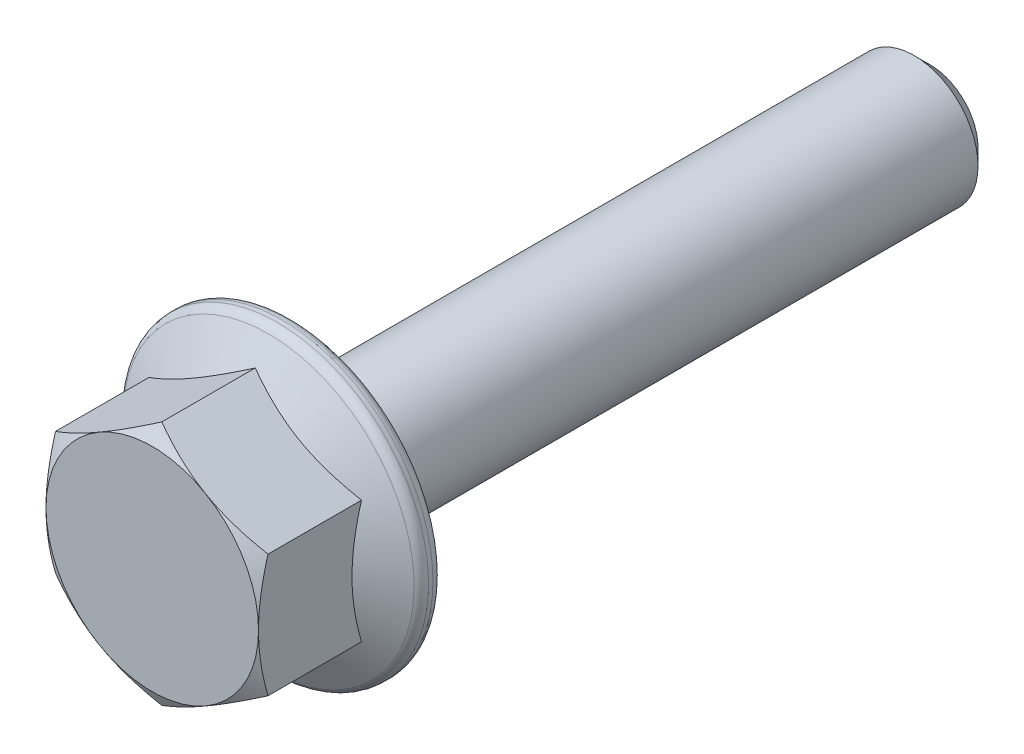
SolidWorks part; units mm, degrees
ref_plane "Front" through (0, 0, 0) normal (0, 0, 1) x (1, 0, 0)
ref_plane "Top" through (0, 0, 0) normal (0, 1, 0) x (1, 0, 0)
ref_plane "Right" through (0, 0, 0) normal (1, 0, 0) x (0, 0, -1)
sketch "Sketch1" plane through (0, 0, 0) normal (0, 0, 1) x (1, 0, 0)
  line L1 (5, -2.8868) -> (5, 2.8868)
  line L2 (5, 2.8868) -> (0, 5.7735)
  line L3 (0, 5.7735) -> (-5, 2.8868)
  line L4 (-5, 2.8868) -> (-5, -2.8868)
  line L5 (-5, -2.8868) -> (0, -5.7735)
  line L6 (0, -5.7735) -> (5, -2.8868)
  circle A0 centre (0, 0) radius 5 construction
extrude "Extrude1" add sketch "Sketch1" along normal blind 6.6
sketch "Sketch2" plane through (0, 0, 0) normal (0, 0, -1) x (-1, 0, 0)
  circle A0 centre (0, 0) radius 7.1
  dimension "Washer OD" = 14.2
extrude "Extrude2" add sketch "Sketch2" against normal blind 0.99
sketch "Sketch5" plane through (0, 0, 0) normal (1, 0, 0) x (0, 0, -1)
  line L0 (0, 0) -> (30, 0)
  line L3 (30, 0) -> (30, 3)
  line L4 (30, 3) -> (0, 3)
  line L5 (0, -7.1) -> (0, 7.1) construction
  line L6 (0, 3) -> (0, 0)
  line L7 (30, 0) -> (33.175, 0) construction
  line L8 (30, -3) -> (0, -3) construction
  line L9 (0, 3) -> (0, 7.1) construction
  line L10 (0, -7.1) -> (0, 7.1) construction
  dimension "Screw Dia" = 6
  dimension "Drill Length" = 3.175
  dimension "Body Length" = 30
  dimension "Screw Length" = 30
sketch "Sketch4" plane through (0, 0, 6.6) normal (0, 0, 1) x (1, 0, 0)
  circle A0 centre (0, 0) radius 4.5
  dimension "D1" = 9
extrude "Cut-Extrude1" [suppressed] cut sketch "Sketch4" against normal blind 0.25 draft 45
sketch "Sketch15" plane through (0, 0, 6.6) normal (0, 0, 1) x (1, 0, 0)
  line L0 (5, 2.8868) -> (0, 5.7735) construction
  circle A0 centre (0, 0) radius 5
extrude "Cut-Extrude5" cut sketch "Sketch15" against normal blind 6.6 draft 60 flip side to cut
revolve "Revolve1" add sketch "Sketch5" angle 360 about L7
sketch "Sketch6" plane through (0, 0, 0) normal (0, 0, 1) x (1, 0, 0)
  circle A0 centre (0, 0) radius 3 construction
  circle A1 centre (0, 0) radius 3
curve "Helix/Spiral1" [suppressed] pitch 1 height 31 turns 31 parameters "Pitch"=1
sketch "Sketch7" plane through (0, 0, 0) normal (1, 0, 0) x (0, 0, -1)
  line L0 (-0.1875, 2.6752) -> (-0.6875, 2.6752) construction
  line L1 (0, 3) -> (0, 0) construction
  line L2 (-0.875, 3) -> (-0.5, 2.3505)
  line L3 (-0.5, 2.3505) -> (-0.375, 2.3505)
  line L4 (-0.375, 2.3505) -> (0, 3)
  line L5 (0, 3) -> (-0.875, 3)
  line L6 (-0.4375, 2.3505) -> (-0.4375, 3) construction
  line L7 (0, 3) -> (0, -8) construction
  line L8 (0, 3) -> (0, -3) construction
  dimension "D3" = 0.125
  dimension "D4" = 60
  dimension "D1" = 0.5
chamfer "Chamfer1" distance 0.75 angle 45 1 edges at (3, 0, -30)
sweep "Cut-Sweep1" [suppressed] cut profiles "Sketch7" path "Helix/Spiral1"
combine bodies "Combine1" operation type add bodies to combine 137 112
sketch "Sketch10" plane through (0, 0, 0) normal (1, 0, 0) x (0, 0, -1)
  line L0 (12, 2.3505) -> (11.6971, 3)
  line L1 (-0.875, 3) -> (11.6971, 3)
  line L2 (-0.875, 3) -> (-0.875, 0)
  line L3 (-0.875, 0) -> (12, 0)
  line L4 (12, 2.3505) -> (12, 0)
  line L6 (30, -2.25) -> (30, 2.25) construction
  dimension "D1" = 25
  dimension "Min Thread" = 18
revolve "Revolve2" add sketch "Sketch10" angle 360 about L3
sketch "Sketch11" plane through (0, 0, 0.99) normal (0, 0, 1) x (1, 0, 0)
  circle A0 centre (0, 0) radius 7.1 construction
  circle A1 centre (0, 0) radius 7.1
extrude "Extrude3" add sketch "Sketch11" along normal blind 3.3 draft 60
sketch "Sketch12" plane through (0, 0, 0) normal (1, 0, 0) x (0, 0, -1)
  line L0 (30, 3) -> (30, -3) construction
  line L1 (0, 0) -> (30, 0) construction
  line L3 (28.5, 3) -> (28.5, -3) construction
  line L4 (30, -2.25) -> (30, 2.25) construction
  dimension "D1" = 1.5
sketch "Sketch13" [suppressed] plane through (0, 0, 6.35) normal (0, 0, 1) x (1, 0, 0)
  line L0 (-5, 2.8868) -> (-5, -2.8868) construction
  line L1 (5, -1.2) -> (-5, -1.2) construction
  line L2 (5, -2.8868) -> (5, 2.8868) construction
  text T0 "10.9" font "Arial" height in points 11
  point P8 (0, -1.2)
  dimension "D1" = 1.2
extrude "Cut-Extrude2" [suppressed] cut sketch "Sketch13" against normal blind 0.25
fillet "Fillet1" radius 0.495 2 edges at (-7.1, 0, 0) (7.1, 0, 0.99)
equation "\"D1@Cut-Extrude1\"=\"Hex@Sketch1\"  * 1 / 40"
equation "\"D3@Helix/Spiral1\" = \"Screw Length@Sketch5\" + \"Pitch@Helix/Spiral1\""
equation "\"D3@Sketch7\" = \"Pitch@Helix/Spiral1\" * 1 / 8"
equation "\"D1@Sketch7\" = \"Pitch@Helix/Spiral1\" * 1 / 2"
equation "\"D1@Sketch12\" = \"Pitch@Helix/Spiral1\" * 1.5"
equation "\"D1@Extrude3\" = \"Head Ht@Extrude1\" * 1 / 2"
equation "\"D1@Chamfer1\" = \"Pitch@Helix/Spiral1\" * .75"
equation "\"Washer Ht@Extrude2\" = \"Head Ht@Extrude1\" * .15"
equation "\"D1@Fillet1\" = \"Washer Ht@Extrude2\" * .5"
equation "\"D1@Sketch4\" = \"Hex@Sketch1\" * .9"
equation "\"D1@Sketch13\" = \"Hex@Sketch1\" * .12"
equation "\"D1@Cut-Extrude5\" = \"Head Ht@Extrude1\""
